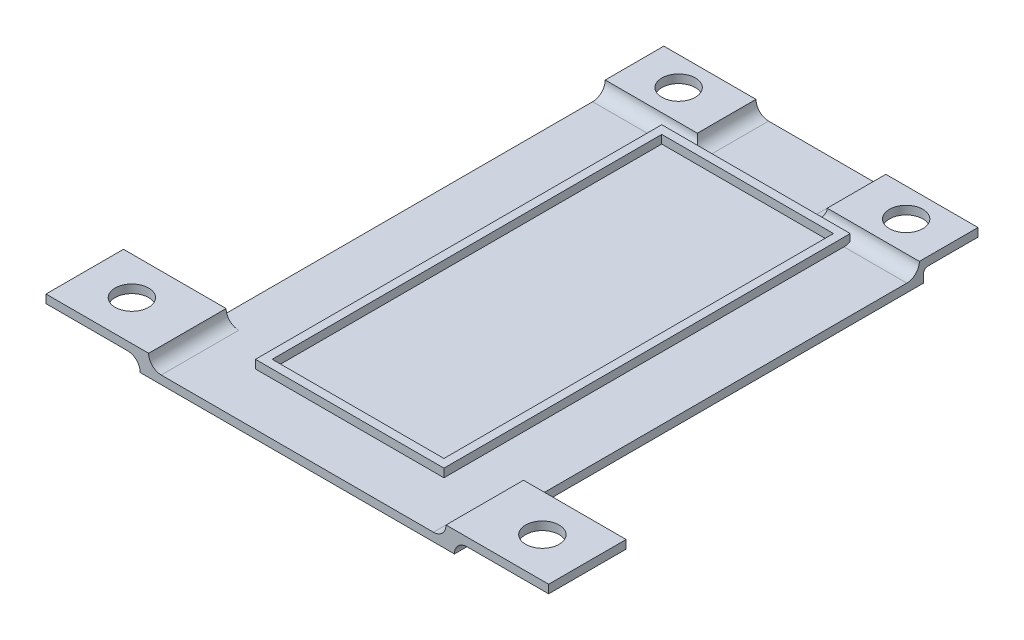
SolidWorks part; units mm, degrees
ref_plane "Front Plane" through (0, 0, 0) normal (0, 0, 1) x (1, 0, 0)
ref_plane "Top Plane" through (0, 0, 0) normal (0, 1, 0) x (1, 0, 0)
ref_plane "Right Plane" through (0, 0, 0) normal (1, 0, 0) x (0, 0, -1)
sketch "Sketch1" plane through (0, 0, 0) normal (0, 1, 0) x (1, 0, 0)
  line L0 (-60, 62.5) -> (60, 62.5)
  line L1 (-60, 62.5) -> (-60, -62.5)
  line L2 (-60, -62.5) -> (60, -62.5)
  line L3 (60, 62.5) -> (60, -62.5)
  point P31 (0, -62.5)
  point P32 (60, 0)
  dimension "D1" = 125
  dimension "D2" = 120
extrude "Boss-Extrude1" add sketch "Sketch1" along normal blind 2
sketch "Sketch2" plane through (0, 2, 0) normal (0, 1, 0) x (1, 0, 0)
  line L0 (-60, -62.5) -> (60, -62.5) construction
  line L1 (60, 62.5) -> (-60, 62.5) construction
  line L2 (-60, 62.5) -> (-60, -62.5) construction
  line L3 (60, -62.5) -> (60, 62.5) construction
  line L4 (-49, 53) -> (-49, 55.6871) construction
  line L7 (0, 62.5) -> (0, 65.4412) construction
  circle A2 centre (49, -53) radius 4
  circle A3 centre (-49, -53) radius 4
  circle A4 centre (-27.1601, 55.6871) radius 4
  circle A5 centre (27.1601, 55.6871) radius 4
  dimension "D11" = 8
  dimension "D2" = 8
  dimension "D3" = 2.6871
  dimension "D4" = 11
  dimension "D6" = 11
  dimension "D7" = 11
  dimension "D8" = 9.5
  dimension "D9" = 9.5
  dimension "D10" = 21.8399
extrude "Cut-Extrude1" cut sketch "Sketch2" against normal up to surface (2 mm away) up to face at (0, 0, 0)
sketch "Sketch3" plane through (0, 2, 0) normal (0, 1, 0) x (1, 0, 0)
  line L0 (0, 70.1471) -> (0, -85.5261) construction
  line L1 (0, 45) -> (-20.5, 45)
  line L2 (0, 45) -> (20.5, 45)
  line L3 (60, 62.5) -> (-60, 62.5) construction
  line L5 (20.5, 47) -> (-20.5, 47)
  line L8 (20.5, -50) -> (22.5, -50)
  line L9 (22.5, -50) -> (22.5, 47)
  line L10 (22.5, 47) -> (20.5, 47)
  line L11 (20.5, -50) -> (0, -50)
  line L12 (-20.5, 47) -> (-22.5, 47)
  line L13 (-22.5, 47) -> (-22.5, -50)
  line L14 (-22.5, -50) -> (0, -50)
  line L15 (-20.5, 45) -> (-20.5, -48)
  line L16 (-20.5, -48) -> (20.5, -48)
  line L17 (20.5, -48) -> (20.5, 45)
  dimension "D1" = 20.5
  dimension "D2" = 20.5
  dimension "D3" = 17.5
  dimension "D4" = 2
  dimension "D5" = 95
  dimension "D6" = 2
  dimension "D7" = 2
  dimension "D8" = 2
extrude "Boss-Extrude2" add sketch "Sketch3" along normal blind 2
sketch "Sketch4" plane through (0, 2, 0) normal (0, 1, 0) x (1, 0, 0)
  line L0 (0, -89.5813) -> (0, 113.1328) construction
  line L1 (60, -44) -> (37.5, -44)
  line L2 (60, -62.5) -> (60, 62.5) construction
  line L3 (37.5, -44) -> (37.5, 62.5)
  line L4 (60, 62.5) -> (-60, 62.5) construction
  line L5 (37.5, 62.5) -> (60, 62.5)
  line L6 (60, 62.5) -> (60, -44)
  line L7 (22.5, -50) -> (22.5, 47) construction
  line L8 (-22.5, -50) -> (22.5, -50) construction
  line L9 (-37.5, 62.5) -> (-60, 62.5)
  line L10 (-37.5, -44) -> (-37.5, 62.5)
  line L11 (-60, -44) -> (-37.5, -44)
  line L12 (-60, 62.5) -> (-60, -44)
  dimension "D1" = 15
  dimension "D2" = 6
extrude "Cut-Extrude2" cut sketch "Sketch4" against normal blind 10
sketch "Sketch6" plane through (0, 2, 0) normal (0, 1, 0) x (1, 0, 0)
  line L0 (60, -62.5) -> (35.5, -62.5)
  line L1 (-60, -62.5) -> (60, -62.5) construction
  line L2 (60, -62.5) -> (60, -44)
  line L3 (60, -44) -> (35.5, -44)
  line L4 (35.5, -44) -> (35.5, -62.5)
  line L5 (37.5, 62.5) -> (37.5, -44) construction
  line L6 (0, -86.2946) -> (0, 82.4081) construction
  line L7 (37.5, 62.5) -> (15.5, 62.5)
  line L8 (37.5, 62.5) -> (-37.5, 62.5) construction
  line L9 (15.5, 62.5) -> (15.5, 48.5)
  line L10 (15.5, 48.5) -> (37.5, 48.5)
  line L11 (37.5, 48.5) -> (37.5, 62.5)
  line L12 (-15.5, 48.5) -> (-37.5, 48.5)
  line L13 (-15.5, 62.5) -> (-15.5, 48.5)
  line L14 (-37.5, 62.5) -> (-15.5, 62.5)
  line L15 (-37.5, 48.5) -> (-37.5, 62.5)
  line L16 (-60, -44) -> (-35.5, -44)
  line L17 (-60, -62.5) -> (-60, -44)
  line L18 (-60, -62.5) -> (-35.5, -62.5)
  line L19 (-35.5, -44) -> (-35.5, -62.5)
  dimension "D1" = 2
  dimension "D2" = 14
  dimension "D3" = 22
extrude "Boss-Extrude3" add sketch "Sketch6" along normal blind 3
sketch "Sketch7" plane through (0, 2, 0) normal (0, -1, 0) x (1, 0, 0)
  circle A0 centre (27.1601, -55.6871) radius 4
  circle A1 centre (-27.1601, -55.6871) radius 4
  circle A2 centre (49, 53) radius 4
  circle A3 centre (-49, 53) radius 4
extrude "Cut-Extrude3" cut sketch "Sketch7" against normal blind 35
sketch "Sketch8" plane through (0, 0, 0) normal (0, -1, 0) x (1, 0, 0)
  line L0 (37.5, -62.5) -> (37.5, -49.5)
  line L1 (37.5, -62.5) -> (37.5, 44) construction
  line L2 (37.5, -49.5) -> (17.5, -49.5)
  line L3 (17.5, -49.5) -> (17.5, -62.5)
  line L4 (37.5, -62.5) -> (-37.5, -62.5) construction
  line L5 (17.5, -62.5) -> (37.5, -62.5)
  line L8 (0, -69.8861) -> (0, 71.9371) construction
  line L9 (37.5, 44) -> (37.5, 62.5)
  line L10 (-60, 62.5) -> (60, 62.5) construction
  line L11 (37.5, 62.5) -> (60, 62.5)
  line L12 (60, 62.5) -> (60, 44)
  line L13 (60, 44) -> (37.5, 44)
  line L14 (-60, 62.5) -> (-60, 44)
  line L15 (-37.5, 62.5) -> (-60, 62.5)
  line L16 (-37.5, 44) -> (-37.5, 62.5)
  line L17 (-60, 44) -> (-37.5, 44)
  line L18 (-17.5, -49.5) -> (-17.5, -62.5)
  line L19 (-37.5, -49.5) -> (-17.5, -49.5)
  line L20 (-37.5, -62.5) -> (-37.5, -49.5)
  line L21 (-17.5, -62.5) -> (-37.5, -62.5)
  dimension "D1" = 13
  dimension "D2" = 20
extrude "Cut-Extrude4" cut sketch "Sketch8" against normal blind 3
fillet "Fillet1" radius 3 1 edges at (15.5, 2, -55.5)
fillet "Fillet2" radius 3 1 edges at (-15.5, 2, -55.5)
fillet "Fillet3" radius 3 1 edges at (-35.5, 2, 53.25)
fillet "Fillet4" radius 3 1 edges at (35.5, 2, 53.25)
fillet "Fillet5" radius 3 1 edges at (25, 2, -48.5)
fillet "Fillet6" radius 3 1 edges at (-25, 2, -48.5)
fillet "Fillet7" radius 3 1 edges at (37.5, 3, 53.25)
fillet "Fillet8" radius 3 1 edges at (-37.5, 3, 53.25)
fillet "Fillet9" radius 3 2 edges at (17.5, 3, -56) (-17.5, 3, -56)
fillet "Fillet10" radius 1 2 edges at (-18.3787, 2.1213, -49.5) (-29, 3, -49.5)
fillet "Fillet11" radius 1 2 edges at (18.3787, 2.1213, -49.5) (29, 3, -49.5)
